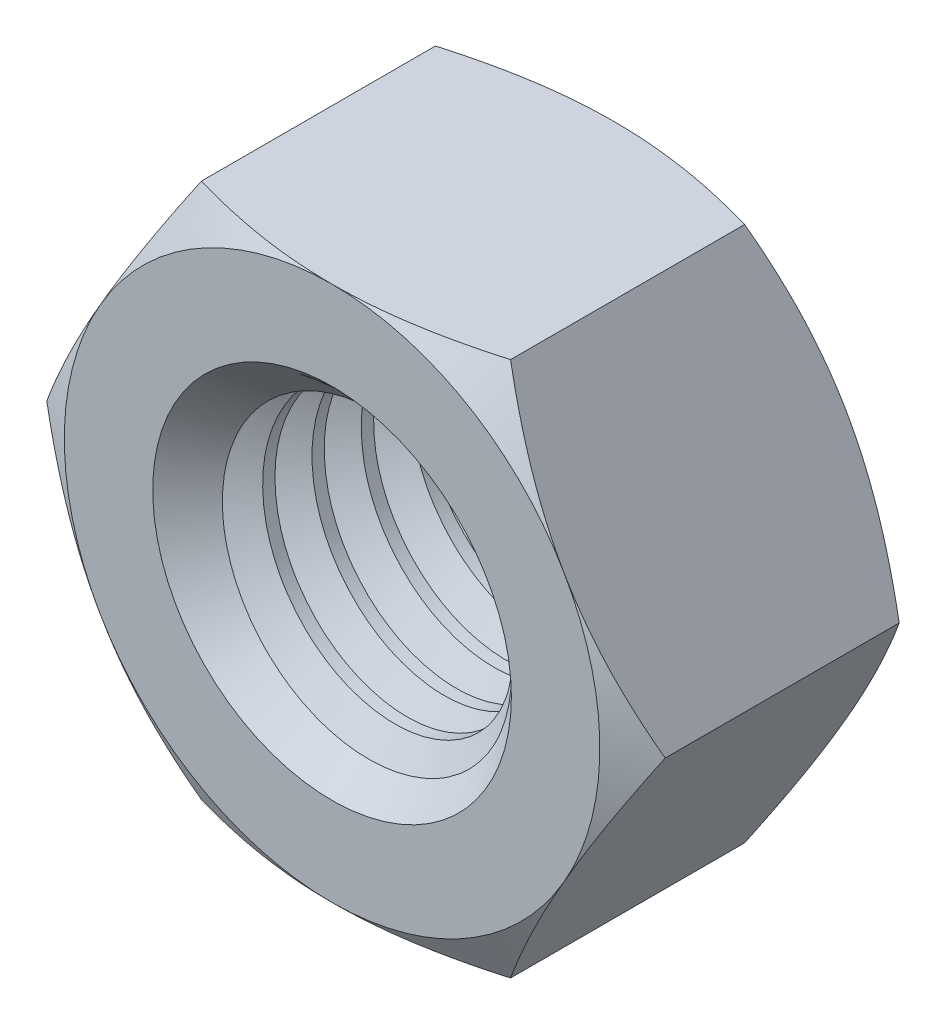
SolidWorks part; units mm, degrees
ref_plane "Front" through (0, 0, 0) normal (0, 0, 1) x (1, 0, 0)
ref_plane "Top" through (0, 0, 0) normal (0, 1, 0) x (1, 0, 0)
ref_plane "Right" through (0, 0, 0) normal (1, 0, 0) x (0, 0, -1)
sketch "Çizim1" plane through (0, 0, 0) normal (0, 0, 1) x (1, 0, 0)
  line L1 (10.9697, 0) -> (5.4848, 9.5)
  line L2 (5.4848, 9.5) -> (-5.4848, 9.5)
  line L3 (-5.4848, 9.5) -> (-10.9697, 0)
  line L4 (-10.9697, 0) -> (-5.4848, -9.5)
  line L5 (-5.4848, -9.5) -> (5.4848, -9.5)
  line L6 (5.4848, -9.5) -> (10.9697, 0)
  circle A0 centre (0, 0) radius 9.5 construction
  dimension "D1" = 19
extrude "Yükseklik-Ekstrüzyon1" add sketch "Çizim1" along normal blind 10
sketch "Çizim2" plane through (0, 0, 10) normal (0, 0, 1) x (1, 0, 0)
  circle A0 centre (0, 0) radius 9.5
extrude "Kes-Ekstrüzyon1" cut sketch "Çizim2" against normal blind 10 draft 60 flip side to cut
sketch "Çizim3" plane through (0, 0, 0) normal (0, 0, -1) x (-1, 0, 0)
  circle A0 centre (0, 0) radius 9.5
extrude "Kes-Ekstrüzyon2" cut sketch "Çizim3" against normal blind 10 draft 60 flip side to cut
sketch "Çizim4" plane through (0, 0, 10) normal (0, 0, 1) x (1, 0, 0)
  circle A0 centre (0, 0) radius 4.8625
  dimension "D1" = 9.725
extrude "Kes-Ekstrüzyon3" cut sketch "Çizim4" against normal blind 10
chamfer "Pah1" distance 1.5 angle 45 2 edges at (4.8625, 0, 0) (4.8625, 0, 10)
sketch "Çizim5" plane through (0, 0, 10) normal (0, 0, 1) x (1, 0, 0)
  circle A1 centre (0, 0) radius 4.8625
  dimension "D1" = 9.725
curve "Helis/Spiral1" pitch 1.75 height 12 radius 4.8625 centre (0, 0, 10) axis (0, 0, -1) start towards (-1, 0, 0)
ref_plane "Düzlem1" through (-3.0317, -3.8017, -2) normal (-0.7806, 0.6225, -0.0572) x (-0.0447, 0.0357, 0.9984)
sketch "Çizim6" plane through (-3.0317, -3.8017, -2) normal (-0.7806, 0.6225, -0.0572) x (-0.0447, 0.0357, 0.9984)
  line L0 (0.8653, 0.3612) -> (-0.8653, 0.3612)
  line L1 (0, -1.1375) -> (0.8653, 0.3612)
  line L3 (-0.8653, 0.3612) -> (0, -1.1375)
  line L5 (0, 0.5687) -> (-0.9851, 0.5687) [skipped]
  circle A0 centre (0, 0) radius 0.5687 construction
  dimension "D1" = 1.1375
sweep "Kes-Süpür1" cut profiles "Çizim6" path "Helis/Spiral1" align with end faces yes
